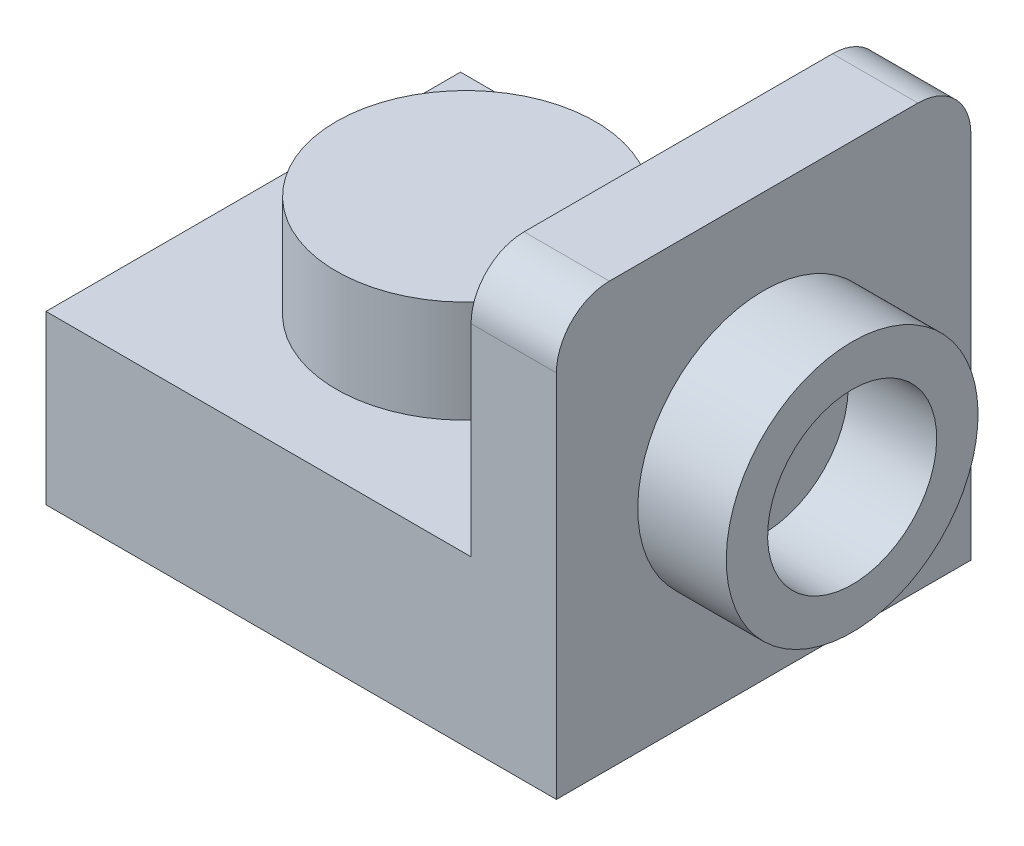
SolidWorks part; units mm, degrees
ref_plane "Front Plane" through (0, 0, 0) normal (0, 0, 1) x (1, 0, 0)
ref_plane "Top Plane" through (0, 0, 0) normal (0, 1, 0) x (1, 0, 0)
ref_plane "Right Plane" through (0, 0, 0) normal (1, 0, 0) x (0, 0, -1)
sketch "Sketch1" plane through (0, 0, 0) normal (0, 0, 1) x (1, 0, 0)
  line L0 (0, 0) -> (-8.02, 0)
  line L1 (-8.02, 0) -> (-8.02, -3.16)
  line L2 (-8.02, -3.16) -> (1.61, -3.16)
  line L3 (1.61, -3.16) -> (1.61, 4.81)
  line L4 (1.61, 4.81) -> (0, 4.81)
  line L5 (0, 4.81) -> (0, 0)
  dimension "D1" = 1.61
  dimension "D2" = 7.97
  dimension "D3" = 9.63
  dimension "D4" = 3.16
extrude "Boss-Extrude1" add sketch "Sketch1" against normal blind 7.82
sketch "Sketch2" plane through (0, 0, 0) normal (0, 1, 0) x (1, 0, 0)
  line L1 (0, 7.82) -> (-8.02, 7.82) construction
  line L2 (-8.02, 7.82) -> (-8.02, 0) construction
  circle A0 centre (-4.01, 3.91) radius 2.445
  dimension "D1" = 4.89
  dimension "D2" = 3.91
  dimension "D3" = 4.01
extrude "Boss-Extrude2" add sketch "Sketch2" along normal blind 1.93
sketch "Sketch3" plane through (1.61, 0, 0) normal (1, 0, 0) x (0, 0, -1)
  line L1 (7.82, 4.81) -> (0, 4.81) construction
  line L2 (0, -3.16) -> (0, 4.81) construction
  circle A0 centre (3.91, 0.825) radius 2.375
  circle A1 centre (3.91, 0.825) radius 1.595
  dimension "D1" = 4.75
  dimension "D4" = 3.19
  dimension "D2" = 3.985
  dimension "D3" = 3.91
extrude "Boss-Extrude3" add sketch "Sketch3" along normal blind 1.67
shell "Shell1" thickness 1.6 removed face at (-3.205, -3.16, -3.91)
fillet "Fillet1" radius 1 2 edges at (0.805, 4.81, -7.82) (0.805, 4.81, 0)
